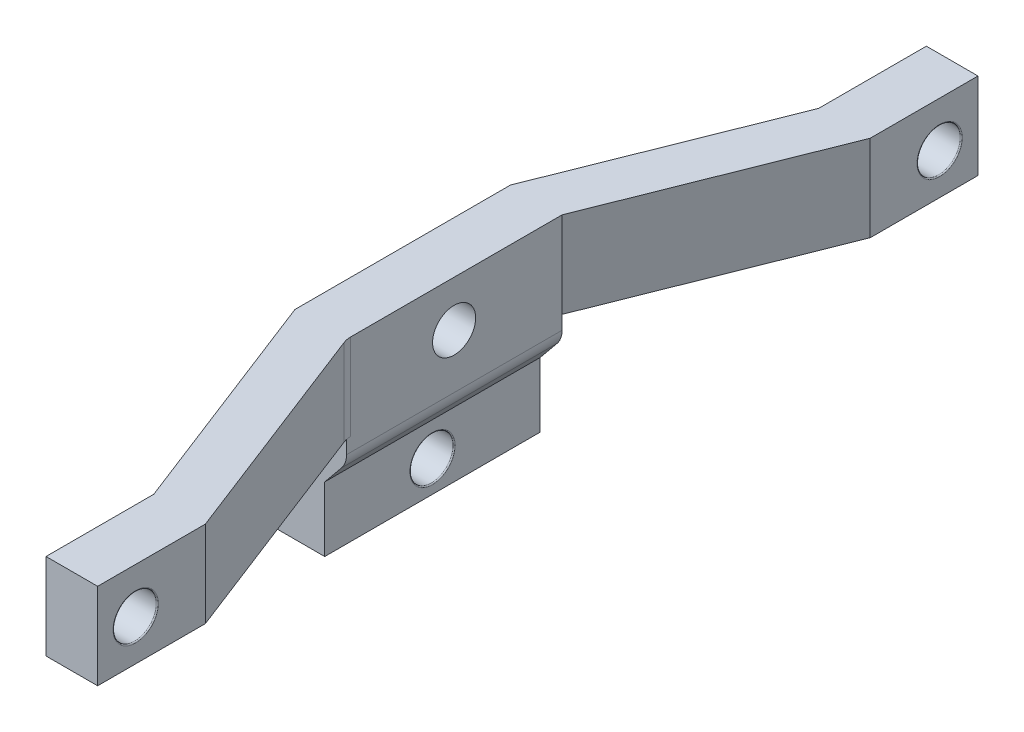
SolidWorks part; units mm, degrees
ref_plane "Front Plane" through (0, 0, 0) normal (0, 0, 1) x (1, 0, 0)
ref_plane "Top Plane" through (0, 0, 0) normal (0, 1, 0) x (1, 0, 0)
ref_plane "Right Plane" through (0, 0, 0) normal (1, 0, 0) x (0, 0, -1)
sketch "Sketch1" plane through (0, 0, 0) normal (0, 0, 1) x (1, 0, 0)
  line L0 (-11.9779, 5) -> (0, 5)
  line L1 (0, 5) -> (0, 0)
  line L2 (0, 0) -> (-5.0696, -6.1887)
  line L3 (-5.0696, -6.1887) -> (-5.0696, -21.1887)
  line L4 (-5.0696, -21.1887) -> (-17.0475, -21.1887)
  line L5 (-17.0475, -21.1887) -> (-17.0475, -6.1887)
  line L6 (-17.0475, -6.1887) -> (-11.9779, 0)
  line L7 (-11.9779, 0) -> (-11.9779, 5)
extrude "Boss-Extrude1" add sketch "Sketch1" along normal blind 50
sketch "Sketch2" plane through (0, 5, 0) normal (0, 1, 0) x (1, 0, 0)
  line L0 (-11.9779, -50) -> (8.7718, -103.4996)
  line L1 (8.7718, -103.4996) -> (8.7718, -128.4996)
  line L2 (8.7718, -128.4996) -> (20.7497, -128.4996)
  line L3 (20.7497, -128.4996) -> (20.7497, -103.4996)
  line L4 (20.7497, -103.4996) -> (0, -50)
  line L5 (0, -50) -> (0, 0)
  line L6 (0, 0) -> (20.343, 51.1391)
  line L7 (20.343, 51.1391) -> (20.343, 76.1391)
  line L8 (20.343, 76.1391) -> (8.3651, 76.1391)
  line L9 (8.3651, 76.1391) -> (8.3651, 51.1391)
  line L10 (8.3651, 51.1391) -> (-11.9779, 0)
  line L11 (-11.9779, 0) -> (-11.9779, -50)
  line L12 (0, 0) -> (-11.9779, 0) construction
  line L13 (0, -50) -> (-11.9779, -50) construction
extrude "Boss-Extrude2" add sketch "Sketch2" along normal blind 20
fillet "Fillet1" radius 5.08 1 edges at (0, 0, 25)
fillet "Fillet2" radius 5.08 1 edges at (0, 15, 50)
sketch "Sketch3" plane through (-11.9779, 0, 0) normal (-1, 0, 0) x (0, 0, 1)
  line L0 (119.6653, 14.4588) -> (-67.2547, 14.4588) construction
  circle A1 centre (-67.2547, 14.4588) radius 5
  circle A2 centre (119.6653, 14.4588) radius 5
extrude "Cut-Extrude3" cut sketch "Sketch3" against normal blind 50.8
sketch "Sketch4" plane through (-17.0475, 0, 0) normal (-1, 0, 0) x (0, 0, 1)
  circle A0 centre (25, -14) radius 5
  point P2 (24.9293, -19.2273)
  point P3 (25.0723, -14.4067)
  point P4 (25.0184, -13.8053)
extrude "Cut-Extrude4" cut sketch "Sketch4" against normal through all
sketch "Sketch22" plane through (-11.9779, 0, 0) normal (-1, 0, 0) x (0, 0, 1)
  circle A0 centre (25.0515, 14.3493) radius 5
  point P0 (25.0515, 14.3493)
  point P11 (25, 15)
  point P12 (25, 15)
  point P13 (25, 15)
extrude "Cut-Extrude12" cut sketch "Sketch22" against normal blind 15
fillet "Fillet4" radius 0.254 1 edges at (-5.0696, -19, 25)
fillet "Fillet5" radius 0.254 1 edges at (-17.0475, -14, 30)
fillet "Fillet6" radius 0.254 1 edges at (20.343, 14.4588, -62.2547)
fillet "Fillet7" radius 0.254 1 edges at (8.3651, 14.4588, -72.2547)
fillet "Fillet8" radius 0.254 1 edges at (20.7497, 14.4588, 124.6653)
fillet "Fillet9" radius 0.254 1 edges at (8.7718, 14.4588, 114.6653)
sketch "Sketch18" plane through (0, 0, 0) normal (0.7736, -0.6337, 0) x (-0.6337, -0.7736, 0)
  line L0 (1.8151, 0) -> (1.8151, -50) construction
  line L1 (1.8151, -11.1587) -> (1.8151, -36.6343)
  arc A0 (1.8151, -11.1587) -> (1.8151, -36.6343) centre (2.1042, -23.8965) cw
sketch "Sketch19" plane through (-11.9779, 0, 0) normal (-1, 0, 0) x (0, 0, 1)
